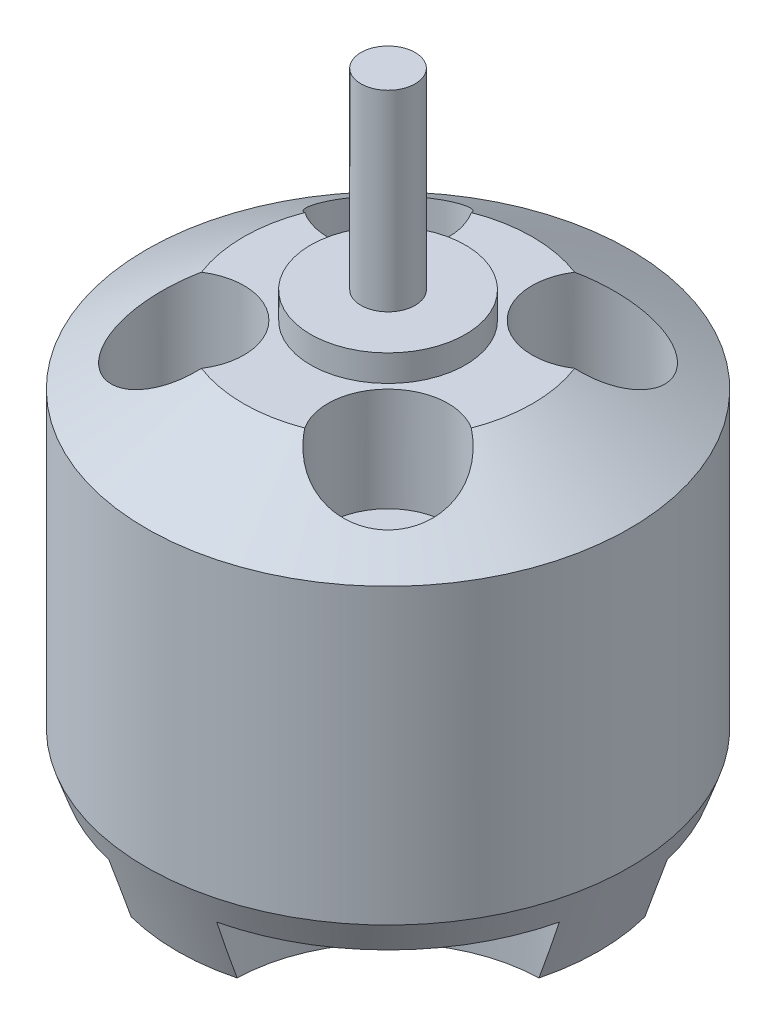
SolidWorks part; units mm, degrees
ref_plane "Front Plane" through (0, 0, 0) normal (0, 0, 1) x (1, 0, 0)
ref_plane "Top Plane" through (0, 0, 0) normal (0, 1, 0) x (1, 0, 0)
ref_plane "Right Plane" through (0, 0, 0) normal (1, 0, 0) x (0, 0, -1)
sketch "Sketch1" plane through (0, 0, 0) normal (0, 0, 1) x (1, 0, 0)
  line L0 (6.9564, -8.4455) -> (5.1721, -13.5255)
  line L1 (-6.9564, 8.4455) -> (6.9564, 8.4455)
  line L2 (-6.9564, 8.4455) -> (-6.9564, -8.4455)
  line L3 (-6.9564, -8.4455) -> (6.9564, -8.4455)
  line L4 (6.9564, 8.4455) -> (6.9564, -8.4455)
  line L5 (-6.9564, 8.4455) -> (6.9564, -8.4455) construction
  line L6 (-6.9564, -8.4455) -> (6.9564, 8.4455) construction
  line L7 (5.1721, -13.5255) -> (-6.9564, -13.5255)
  line L8 (-6.9564, -13.5255) -> (-6.9564, -8.4455)
  line L9 (6.9564, 8.4455) -> (1.3621, 11.8745)
  line L10 (1.3621, 11.8745) -> (-6.9564, 11.8745)
  line L11 (-6.9564, 11.8745) -> (-6.9564, 8.4455)
  line L12 (-6.9564, 11.8745) -> (-6.9564, 13.3985)
  line L13 (-6.9564, 13.3985) -> (-2.4987, 13.3985)
  line L14 (-2.4987, 13.3985) -> (-2.4987, 11.8745)
  line L16 (-5.3943, 13.3985) -> (-5.3943, 24.4475)
  line L17 (-5.3943, 24.4475) -> (-6.9564, 24.4475)
  line L18 (-6.9564, 24.4475) -> (-6.9564, 13.3985)
  line L19 (-6.9564, -13.5255) -> (-6.9564, -14.7955)
  line L20 (-6.9564, -14.7955) -> (-5.3943, -14.7955)
  line L21 (-5.3943, -14.7955) -> (-5.3943, -13.5255)
  point P0 (0, 0)
  point P16 (3.6897, -12.8905)
  point P20 (3.8427, -13.5255)
  point P21 (3.6477, -13.5255)
  dimension "D1" = 16.891
  dimension "D2" = 8.3185
  dimension "D3" = 5.08
  dimension "D4" = 25.4
  dimension "D5" = 1.524
  dimension "D6" = 11.049
  dimension "D7" = 1.27
  dimension "D8" = 13.9128
  dimension "D9" = 4.4577
  dimension "D10" = 1.5621
  dimension "D11" = 1.5621
  dimension "D12" = 12.1285
revolve "Revolve1" add sketch "Sketch1" angle 360 about L2 region at (-0.4359, -10.9275, 0) region at (0, 0, 0) region at (-1.2813, 10.0162, 0) region at (-6.1754, -14.1605, 0) region at (-4.7276, 12.6365, 0) region at (-6.1754, 18.923, 0)
sketch "Sketch2" plane through (0, -13.5255, 0) normal (0, -1, 0) x (1, 0, 0)
  line L0 (-6.9564, 11.9576) -> (-6.9564, -11.9576) construction
  line L1 (-18.914, 11.9576) -> (5.0012, 11.9576) construction
  line L2 (-18.914, 11.9576) -> (-18.914, -11.9576) construction
  line L3 (-18.914, -11.9576) -> (5.0012, -11.9576) construction
  line L4 (5.0012, 11.9576) -> (5.0012, -11.9576) construction
  line L5 (-18.914, 11.9576) -> (5.0012, -11.9576) construction
  line L6 (-18.914, -11.9576) -> (5.0012, 11.9576) construction
  line L8 (5.0012, 0) -> (-18.914, 0) construction
  circle A0 centre (5.0012, 11.9576) radius 8.9096
  circle A1 centre (-18.914, 11.9576) radius 8.9096
  circle A2 centre (-18.914, -11.9576) radius 8.9096
  circle A3 centre (5.0012, -11.9576) radius 8.9096
  circle A4 centre (-6.9564, 9.4488) radius 1.27
  circle A5 centre (2.7718, 0) radius 1.27
  circle A6 centre (-6.9564, -9.4488) radius 1.27
  circle A7 centre (-16.6846, 0) radius 1.27
  point P0 (-6.9564, 0)
  point P10 (-10.0044, 11.9576)
  point P11 (-3.9084, 11.9576)
  point P12 (-12.614, -5.6576)
  point P13 (-1.2989, 5.6576)
  point P26 (13.0886, 0)
  point P27 (-60.8765, 0)
  point P28 (-23.0067, 25.2617)
  point P29 (-23.0067, -25.5136)
  dimension "D2" = 2.54
  dimension "D1" = 9.4488
  dimension "D3" = 9.4488
  dimension "D4" = 9.7282
  dimension "D5" = 9.7282
  dimension "D6" = 6.096
  dimension "D7" = 16.002
sketch "Sketch3" plane through (0, 11.8745, 0) normal (0, 1, 0) x (1, 0, 0)
  line L0 (-18.914, 11.9576) -> (5.0012, -11.9576) construction
  line L1 (-12.8365, 5.8801) -> (-1.0763, 5.8801) construction
  line L2 (-12.8365, 5.8801) -> (-12.8365, -5.8801) construction
  line L3 (-12.8365, -5.8801) -> (-1.0763, -5.8801) construction
  line L4 (-1.0763, 5.8801) -> (-1.0763, -5.8801) construction
  line L5 (-12.8365, 5.8801) -> (-1.0763, -5.8801) construction
  line L6 (-12.8365, -5.8801) -> (-1.0763, 5.8801) construction
  circle A0 centre (-1.0763, 5.8801) radius 3.4671
  circle A1 centre (-1.0763, -5.8801) radius 3.4671
  circle A2 centre (-12.8365, -5.8801) radius 3.4671
  circle A3 centre (-12.8365, 5.8801) radius 3.4671
  point P0 (-6.9564, 0)
  point P12 (-9.3694, 5.8801)
  point P13 (-4.5434, 5.8801)
  dimension "D1" = 6.9342
  dimension "D2" = 4.826
extrude "Cut-Extrude1" cut sketch "Sketch2" against normal blind 3.429
extrude "Cut-Extrude2" cut sketch "Sketch3" against normal blind 5.969
